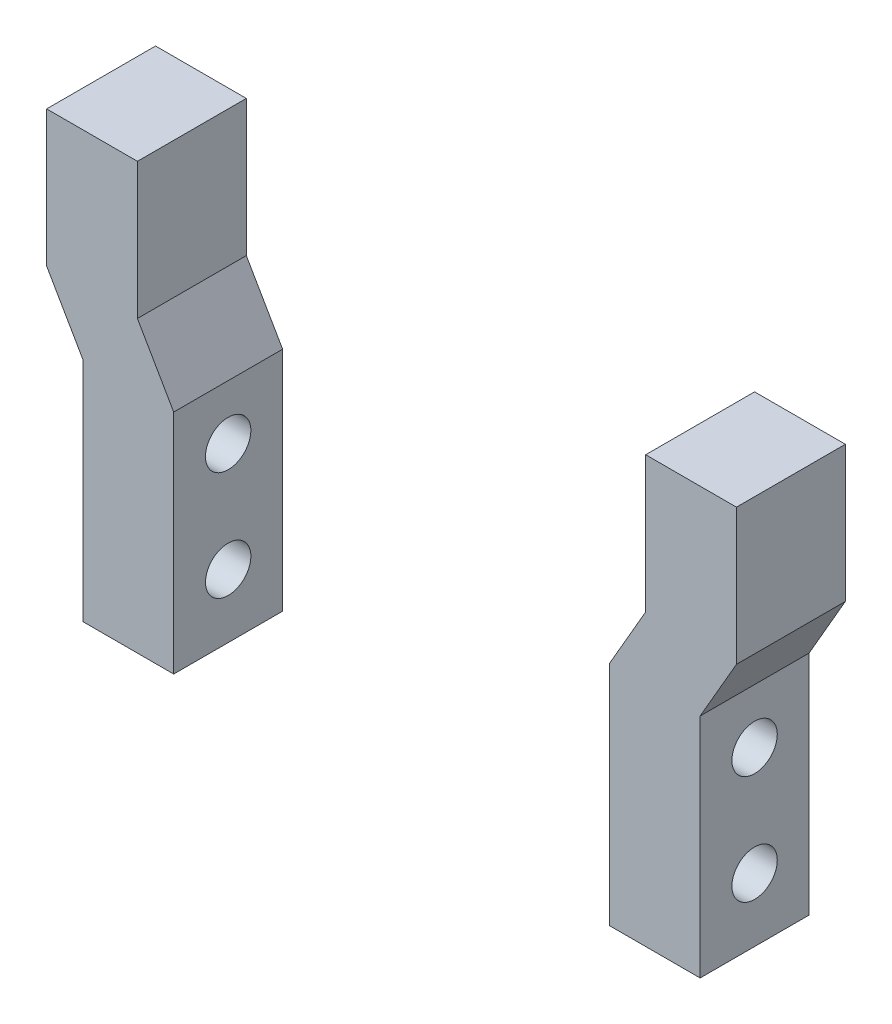
SolidWorks part; units mm, degrees
note: The reader was unsure of these and kept them because the rebuilt part matched: shared geometry of "草图1<3>", "草图3<3>".
ref_plane "前视基准面" through (0, 0, 0) normal (0, 0, 1) x (1, 0, 0)
ref_plane "上视基准面" through (0, 0, 0) normal (0, 1, 0) x (1, 0, 0)
ref_plane "右视基准面" through (0, 0, 0) normal (1, 0, 0) x (0, 0, -1)
sketch "草图1" plane through (0, 0, 0) normal (0, 0, 1) x (1, 0, 0)
  line L0 (-19.8986, 2.4848) -> (-9.8986, 2.4848)
  line L1 (-19.8986, 2.4848) -> (-19.8986, 27.4848)
  line L2 (-9.8986, 2.4848) -> (-9.8986, 27.4848)
  line L3 (-19.8986, 27.4848) -> (-23.8986, 34.413)
  line L4 (-23.8986, 34.413) -> (-23.8986, 49.413)
  line L5 (-23.8986, 49.413) -> (-13.8986, 49.413)
  line L6 (-13.8986, 49.413) -> (-13.8986, 34.413)
  line L7 (-13.8986, 34.413) -> (-9.8986, 27.4848)
  line L8 (14.1014, -2.645) -> (14.1014, 68.2011) construction
  line L9 (42.1014, 34.413) -> (38.1014, 27.4848)
  line L10 (42.1014, 49.413) -> (42.1014, 34.413)
  line L11 (52.1014, 49.413) -> (42.1014, 49.413)
  line L12 (52.1014, 34.413) -> (52.1014, 49.413)
  line L13 (48.1014, 27.4848) -> (52.1014, 34.413)
  line L14 (38.1014, 2.4848) -> (38.1014, 27.4848)
  line L15 (48.1014, 2.4848) -> (48.1014, 27.4848)
  line L16 (48.1014, 2.4848) -> (38.1014, 2.4848)
  line L17 (-13.8986, 34.413) -> (-9.8986, 27.4848)
  line L18 (-9.8986, 27.4848) -> (-19.8986, 27.4848) construction
  line L19 (-9.8986, 27.4848) -> (-9.8986, 65.0927) construction
  dimension "D1" = 10
  dimension "D2" = 25
  dimension "D3" = 120
  dimension "D4" = 4
  dimension "D5" = 15
  dimension "D6" = 56
extrude "凸台-拉伸1" add sketch "草图1" along normal blind 12 contours L9 L14 L16 L15 L13 L12 L11 L10
extrude "凸台-拉伸2" add sketch "草图1<3>" along normal blind 12 separate body contours L7 L6 L5 L4 L3 L1 L0 L2
sketch "草图1<3>" plane through (0, 0, 0) normal (0, 0, 1) x (1, 0, 0) same geometry as "草图1"
sketch "草图3" plane through (-9.8986, 0, 0) normal (1, 0, 0) x (0, 0, -1)
  line L0 (-6, 27.4848) -> (-6, 0) construction
  line L1 (-12, 27.4848) -> (0, 27.4848) construction
  line L2 (-12, 21.4848) -> (0, 21.4848) construction
  line L3 (-12, 2.4848) -> (-12, 27.4848) construction
  line L4 (0, 2.4848) -> (0, 27.4848) construction
  circle A0 centre (-6, 21.4848) radius 2.5
  circle A1 centre (-6, 9.4848) radius 2.5
  point P10 (-6, 21.4848)
  dimension "D2" = 5
  dimension "D3" = 12
  dimension "D1" = 6
extrude "切除-拉伸1" cut sketch "草图3" against normal up to next (10 mm away) contours A0
extrude "切除-拉伸2" cut sketch "草图3<3>" against normal up to next (10 mm away)
sketch "草图3<3>" plane through (-9.8986, 0, 0) normal (1, 0, 0) x (0, 0, -1) same geometry as "草图3"
sketch "草图6" plane through (48.1014, 0, 0) normal (1, 0, 0) x (0, 0, -1)
  line L0 (-6, 27.4848) -> (-6, -8.5152) construction
  line L1 (-12, 27.4848) -> (0, 27.4848) construction
  circle A0 centre (-6, 21.4848) radius 2.5
  circle A1 centre (-6, 9.4848) radius 2.5
  dimension "D1" = 5
  dimension "D2" = 5
  dimension "D3" = 12
  dimension "D4" = 6
extrude "切除-拉伸3" cut sketch "草图6" against normal up to next (10 mm away)
